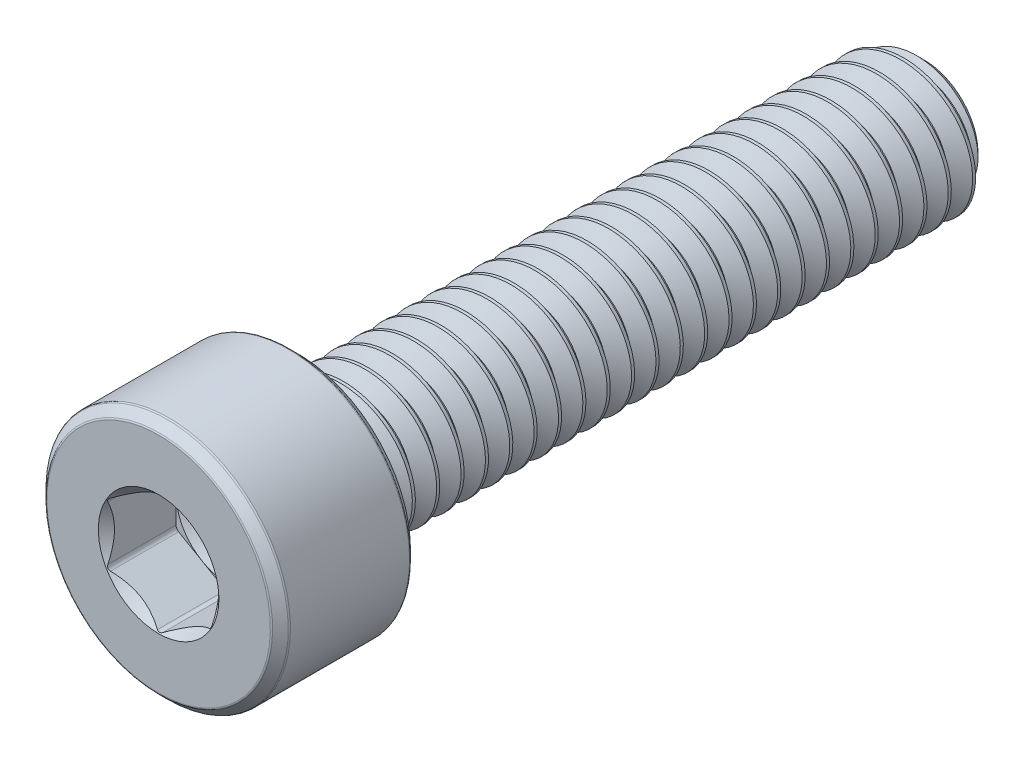
SolidWorks part; units mm, degrees
ref_plane "Front Plane" through (0, 0, 0) normal (0, 0, 1) x (1, 0, 0)
ref_plane "Top Plane" through (0, 0, 0) normal (0, 1, 0) x (1, 0, 0)
ref_plane "Right Plane" through (0, 0, 0) normal (1, 0, 0) x (0, 0, -1)
sketch "Sketch1" plane through (0, 0, 0) normal (1, 0, 0) x (0, 0, -1)
  line L0 (-11, 0) -> (11, 0) construction
  line L1 (-11, 0) -> (-11, 3.5)
  line L2 (-11, 3.5) -> (-7, 3.5)
  line L3 (-7, 3.5) -> (-7, 2)
  line L4 (-7, 2) -> (10.5453, 2)
  line L5 (10.9562, 2.0758) -> (11.3062, 1.4696) construction
  line L6 (11.3062, 1.4696) -> (11.6562, 2.0758) construction
  line L7 (11.6562, 2.0758) -> (10.9562, 2.0758) construction
  line L8 (10.5453, 2) -> (11, 1.5453)
  line L9 (11, 1.5453) -> (11, 0)
  line L10 (11, 2) -> (11.6125, 2) construction
  line L11 (11.3062, 2.0758) -> (11.3062, 2) construction
  line L12 (11.3062, 2) -> (11.3062, 1.5453) construction
  line L13 (11.3062, 1.5453) -> (11.3062, 1.4696) construction
  line L14 (11.2625, 1.5453) -> (11.35, 1.5453)
  line L15 (10.9781, 2.0379) -> (11.6344, 2.0379)
  line L16 (11.35, 1.5453) -> (11.6344, 2.0379)
  line L17 (11.2625, 1.5453) -> (10.9781, 2.0379)
  line L18 (-11, 1.5) -> (-9, 1.5)
  line L19 (-9, 1.5) -> (-9, 0)
  line L20 (8.55, 2) -> (8.55, -2) construction
  point P20 (11.3062, 2.0379)
  point P22 (8.55, -2)
  point P28 (8.55, 0)
  point P29 (10.5453, -2)
  dimension "Head Diameter" = 7
  dimension "Length" = 18
  dimension "Head Height" = 4
  dimension "Thread Size" = 4
  dimension "D1" = 45
  dimension "Thread Pitch" = 0.7
  dimension "D3" = 0.0875
  dimension "Drive Size" = 3
  dimension "D4" = 2.45
  dimension "D5" = 2
sketch "Sketch3" plane through (0, 0, 0) normal (1, 0, 0) x (0, 0, -1)
  line L0 (-11, 3.2103) -> (-11, 1.5)
  line L1 (-11, 1.5) -> (-9, 1.5)
  line L2 (-9, 1.5) -> (-9, 0)
  line L3 (-9, 0) -> (11, 0)
  line L4 (11, 0) -> (11, 1.5453)
  line L5 (11, 1.5453) -> (10.5453, 2)
  line L6 (10.5453, 2) -> (-7, 2)
  line L7 (-7, 2) -> (-7, 3.2103)
  line L8 (-7.2897, 3.5) -> (-10.7103, 3.5)
  line L9 (-10.9808, 3.2567) -> (-10.7567, 3.4808)
  line L11 (-11, 3.5) -> (-7, 3.5) construction
  line L12 (-7.2433, 3.4808) -> (-7.0192, 3.2567)
  arc A5 (-7.0192, 3.2567) -> (-7, 3.2103) centre (-7.0656, 3.2103) cw
  arc A6 (-7.2897, 3.5) -> (-7.2433, 3.4808) centre (-7.2897, 3.4344) cw
  arc A7 (-10.7103, 3.5) -> (-10.7567, 3.4808) centre (-10.7103, 3.4344) ccw
  arc A8 (-11, 3.2103) -> (-10.9808, 3.2567) centre (-10.9344, 3.2103) cw
  point P17 (-9, 3.5)
  point P29 (-11, 3.2375)
  dimension "D3" = 0.0656
  dimension "D1" = 45
  dimension "D2" = 0.2625
revolve "Revolve1" add sketch "Sketch3" angle 360 about L0
sketch "Sketch4" plane through (0, 0, 11) normal (0, 0, 1) x (1, 0, 0)
  line L1 (0, 1.7321) -> (-1.5, 0.866)
  line L2 (-1.5, 0.866) -> (-1.5, -0.866)
  line L3 (-1.5, -0.866) -> (0, -1.7321)
  line L4 (0, -1.7321) -> (1.5, -0.866)
  line L5 (1.5, -0.866) -> (1.5, 0.866)
  line L6 (1.5, 0.866) -> (0, 1.7321)
  circle A0 centre (0, 0) radius 1.5 construction
extrude "Cut-Extrude1" cut sketch "Sketch4" against normal up to vertex (2 mm away) up to point (0, 1.5, 9)
sketch "Sketch5" plane through (0, 0, 11) normal (0, 0, 1) x (1, 0, 0)
  circle A0 centre (0, 0) radius 1.7321
extrude "Cut-Extrude2" cut sketch "Sketch5" against normal up to next (2 mm away) draft 45
sketch "Sketch10" plane through (0, 0, 9) normal (0, 0, 1) x (1, 0, 0)
  line L0 (1.5, 0.866) -> (1.5, -0.866) construction
  circle A0 centre (0, 0) radius 1.5
extrude "Cut-Extrude3" cut sketch "Sketch10" against normal through all draft 60
fillet "Fillet1" radius 0.15 6 edges at (-1.5, 0.866, 10) (0, 1.7321, 10) (1.5, 0.866, 10) (1.5, -0.866, 10) (0, -1.7321, 10) (-1.5, -0.866, 10)
sketch "Sketch6" plane through (0, 0, -11) normal (0, 0, -1) x (-1, 0, 0)
  circle A0 centre (0, 0) radius 2 construction
  circle A1 centre (0, 0) radius 2
curve "Helix/Spiral1" pitch 0.7 height 18.7 radius 2 centre (0, 0, -11) axis (0, 0, 1) start towards (0, 1, 0)
sketch "Sketch7" plane through (0, 0, 0) normal (1, 0, 0) x (0, 0, -1)
  line L0 (11.2625, 1.5453) -> (11.35, 1.5453) construction
  line L1 (11.2625, 1.5453) -> (10.9781, 2.0379) construction
  line L2 (10.9781, 2.0379) -> (11.6344, 2.0379) construction
  line L3 (11.35, 1.5453) -> (11.6344, 2.0379) construction
  line L4 (11.2625, 1.5453) -> (11.35, 1.5453)
  line L5 (11.2625, 1.5453) -> (10.9781, 2.0379)
  line L6 (10.9781, 2.0379) -> (11.6344, 2.0379)
  line L7 (11.35, 1.5453) -> (11.6344, 2.0379)
sweep "Cut-Sweep1" cut profiles "Sketch7" path "Helix/Spiral1" align with end faces yes
sketch "Sketch11" plane through (0, 0, 0) normal (1, 0, 0) x (0, 0, -1)
  line L0 (-7, 2.175) -> (-6.825, 2) construction
  line L1 (-7, 3.5) -> (-7, 2) construction
  line L2 (-7, 2) -> (10.5453, 2) construction
  line L3 (-6.825, 2) -> (-6.65, 2)
  line L4 (-6.65, 2) -> (-4.65, 0)
  line L5 (-11, 0) -> (11, 0) construction
  line L6 (-4.65, 0) -> (-7, 0)
  line L7 (-7, 0) -> (-7, 2.175) construction
  line L8 (-7, 2.175) -> (-8.134, 2.175)
  line L9 (-8.134, 2.175) -> (-8.134, 0)
  line L10 (-8.134, 0) -> (-7, 0)
  arc A0 (-6.825, 2) -> (-7, 2.175) centre (-6.825, 2.175) cw
  dimension "D1" = 45
  dimension "D2" = 0.175
  dimension "D3" = 45
  dimension "D4" = 0.35
revolve "Revolve2" add sketch "Sketch11" angle 360 about L6
equation "\"D3@Sketch1\" = \"Thread Pitch@Sketch1\" / 8"
equation "\"D4@Sketch1\" = \"Thread Pitch@Sketch1\" * 3.5"
equation "\"D3@Helix/Spiral1\" = \"Length@Sketch1\" + \"Thread Pitch@Sketch1\""
equation "\"D4@Helix/Spiral1\" = \"Thread Pitch@Sketch1\""
equation "\"D5@Sketch1\"=\"Head Height@Sketch1\"*0.5"
equation "\"D2@Sketch3\"=\"Head Diameter@Sketch1\" *0.0375"
equation "\"D2@Sketch11\"=\"Thread Pitch@Sketch1\" / 4"
equation "\"D4@Sketch11\"=\"Thread Pitch@Sketch1\"/2"
equation "\"D1@Fillet1\"=\"Drive Size@Sketch1\"*0.05"
equation "\"D1@Fillet1\" = \"Drive Size@Sketch1\" * 0.05"
equation "\"D3@Sketch3\"=\"D2@Sketch3\"*0.25"
